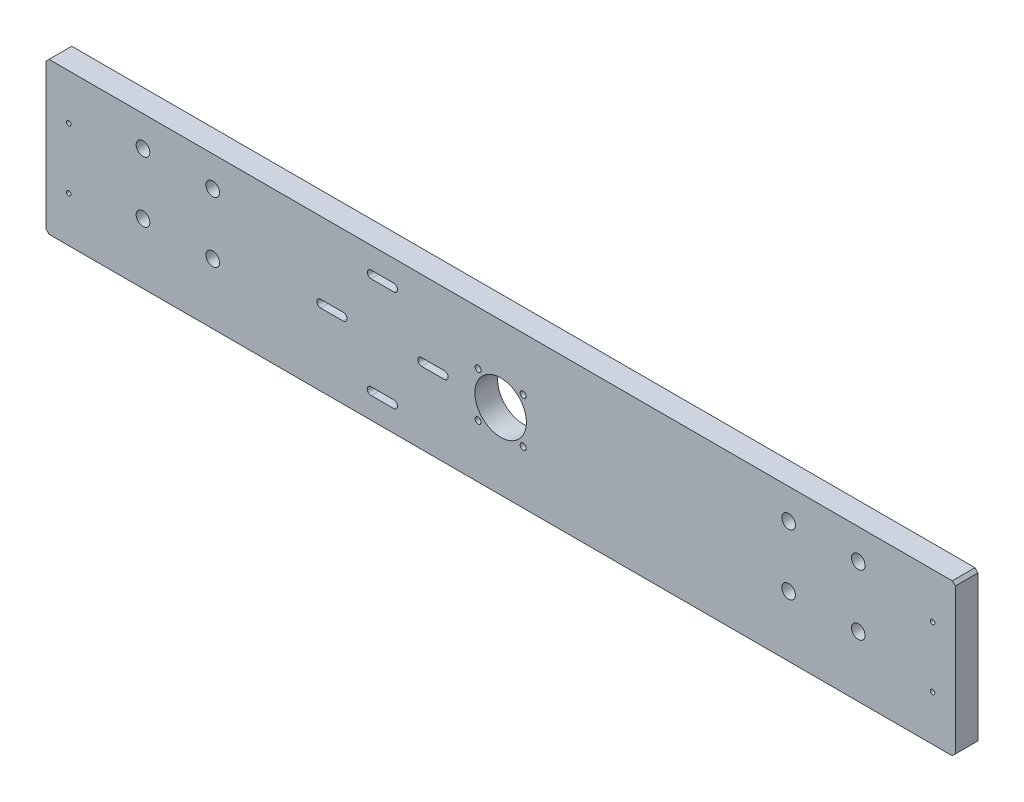
SolidWorks part; units mm, degrees
ref_plane "Piano frontale" through (0, 0, 0) normal (0, 0, 1) x (1, 0, 0)
ref_plane "Piano superiore" through (0, 0, 0) normal (0, 1, 0) x (1, 0, 0)
ref_plane "Piano destro" through (0, 0, 0) normal (1, 0, 0) x (0, 0, -1)
sketch "Schizzo1" plane through (0, 0, 0) normal (0, 0, 1) x (1, 0, 0)
  line L0 (300, 100) -> (300, 0) construction
  line L1 (2, 0) -> (598, 0)
  line L2 (0, 2) -> (0, 98)
  line L3 (2, 100) -> (598, 100)
  line L4 (600, 2) -> (600, 98)
  line L5 (87, 100) -> (87, 0) construction
  line L7 (300, 50) -> (318.5099, 50) construction
  line L9 (300, 50) -> (280.51, 69.49) construction
  line L21 (0, 98) -> (2, 100)
  line L22 (2, 0) -> (0, 2)
  line L23 (598, 0) -> (600, 2)
  line L24 (598, 100) -> (600, 98)
  circle A0 centre (300, 50) radius 17
  circle A1 centre (300, 50) radius 21 construction
  circle A2 centre (314.8492, 64.8492) radius 2
  circle A3 centre (314.8492, 35.1508) radius 2
  circle A4 centre (285.1508, 35.1508) radius 2
  circle A5 centre (536, 40) radius 4.5
  circle A6 centre (536, 80) radius 4.5
  circle A7 centre (490, 40) radius 4.5
  circle A8 centre (490, 80) radius 4.5
  circle A9 centre (585, 70) radius 1.5
  circle A10 centre (585, 30) radius 1.5
  circle A11 centre (15, 30) radius 1.5
  circle A13 centre (285.1508, 64.8492) radius 2
  circle A18 centre (15, 70) radius 1.5
  circle A29 centre (110, 80) radius 4.5
  circle A30 centre (110, 40) radius 4.5
  circle A32 centre (64, 80) radius 4.5
  circle A33 centre (64, 40) radius 4.5
  point P0 (0, 0)
  point P1 (600, 100)
  point P2 (0, 100)
  point P3 (600, 0)
  point P9 (285.1508, 64.8492)
  point P13 (285.1508, 64.8492)
  dimension "D4" = 34
  dimension "D10" = 23
  dimension "D15" = 3
  dimension "D17" = 4
  dimension "D8" = 45
  dimension "D5" = 42
  dimension "D9" = 64
  dimension "D11" = 9
  dimension "D1" = 100
  dimension "D2" = 600
  dimension "D6" = 20
  dimension "D7" = 40
  dimension "D14" = 30
  dimension "D16" = 15
extrude "Boss-Extrude1" add sketch "Schizzo1" against normal blind 15
sketch "Sketch2" plane through (0, 0, 0) normal (0, -1, 0) x (1, 0, 0)
  line L0 (2, -7.5) -> (598, -7.5) construction
  line L1 (2, -15) -> (2, 0) construction
  line L2 (598, -15) -> (598, 0) construction
  line L3 (300, -15) -> (300, 0) construction
  line L4 (2, -15) -> (598, -15) construction
  line L5 (321, 0) -> (279, 0) construction
  line L6 (0, -15) -> (0, 0) construction
  point P12 (30, -7.5)
  point P15 (570, -7.5)
  dimension "D1" = 30
hole_wizard "M8 Tapped Hole1" positions "3DSketch1" profile "Sketch3" tap size "M8" standard "ISO"
sketch3d "3DSketch1"
  point P0 (30, 0, -7.5)
  point P3 (570, 0, -7.5)
sketch "Sketch3" plane through (30, 0, -7.5) normal (1, 0, 0) x (0, 0, -1)
  line L0 (0, 0) -> (0, 25.7929)
  line L1 (0, 25.7929) -> (3.4, 23.75)
  line L2 (3.4, 23.75) -> (3.4, 0)
  line L5 (3.4, 0) -> (0, 0)
  line L10 (0, 25.7929) -> (-3.4, 23.75) construction
  line L11 (0, -6.35) -> (0, 107.95) construction
  dimension "Tap Drill Dia." = 6.8
  dimension "Tap Drill Depth" = 23.75
  dimension "Drill Angle" = 118
sketch "Sketch4" plane through (0, 0, -15) normal (0, 0, -1) x (-1, 0, 0)
  line L0 (-300, 50) -> (-140.6098, 50) construction
sketch "Sketch7" plane through (0, 0, -15) normal (0, 0, -1) x (-1, 0, 0)
  line L0 (-214.5, 83.333) -> (-229.5, 83.333) construction
  line L1 (-214.5, 80.833) -> (-229.5, 80.833)
  line L2 (-214.5, 85.833) -> (-229.5, 85.833)
  line L3 (-247.833, 50) -> (-262.833, 50) construction
  line L4 (-247.833, 47.5) -> (-262.833, 47.5)
  line L5 (-247.833, 52.5) -> (-262.833, 52.5)
  line L6 (-181.167, 50) -> (-196.167, 50) construction
  line L7 (-181.167, 47.5) -> (-196.167, 47.5)
  line L8 (-181.167, 52.5) -> (-196.167, 52.5)
  line L9 (-214.5, 16.667) -> (-229.5, 16.667) construction
  line L10 (-214.5, 14.167) -> (-229.5, 14.167)
  line L11 (-214.5, 19.167) -> (-229.5, 19.167)
  arc A0 (-214.5, 80.833) -> (-214.5, 85.833) centre (-214.5, 83.333) ccw
  arc A1 (-229.5, 85.833) -> (-229.5, 80.833) centre (-229.5, 83.333) ccw
  arc A2 (-247.833, 47.5) -> (-247.833, 52.5) centre (-247.833, 50) ccw
  arc A3 (-262.833, 52.5) -> (-262.833, 47.5) centre (-262.833, 50) ccw
  arc A4 (-181.167, 47.5) -> (-181.167, 52.5) centre (-181.167, 50) ccw
  arc A5 (-196.167, 52.5) -> (-196.167, 47.5) centre (-196.167, 50) ccw
  arc A6 (-214.5, 14.167) -> (-214.5, 19.167) centre (-214.5, 16.667) ccw
  arc A7 (-229.5, 19.167) -> (-229.5, 14.167) centre (-229.5, 16.667) ccw
  point P0 (-255.333, 50)
  point P1 (-222, 83.333)
  point P2 (-188.667, 50)
  point P3 (-222, 16.667)
  point P6 (-222, 83.333)
  point P13 (-255.333, 50)
  point P20 (-188.667, 50)
  point P27 (-222, 16.667)
  dimension "D1" = 15
  dimension "D2" = 5
extrude "Cut-Extrude1" cut sketch "Sketch7" against normal through all
